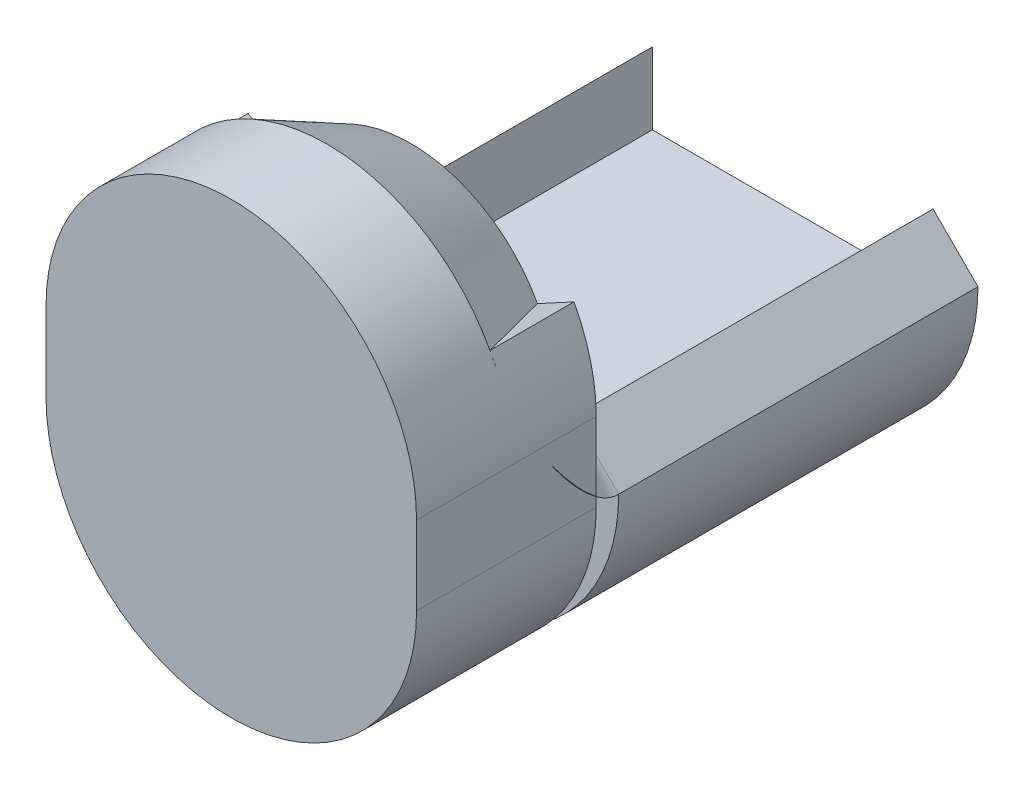
SolidWorks part; units mm, degrees
ref_plane "Front Plane" through (0, 0, 0) normal (0, 0, 1) x (1, 0, 0)
ref_plane "Top Plane" through (0, 0, 0) normal (0, 1, 0) x (1, 0, 0)
ref_plane "Right Plane" through (0, 0, 0) normal (1, 0, 0) x (0, 0, -1)
sketch "Sketch2" plane through (0, 0, 0) normal (0, 0, 1) x (1, 0, 0)
  line L2 (-55.5625, -10.3188) -> (-55.5625, 10.3187)
  line L4 (55.5625, -10.3187) -> (55.5625, 10.3188)
  line L5 (-55.5625, -10.3188) -> (55.5625, 10.3188) construction
  line L6 (-55.5625, 10.3187) -> (55.5625, -10.3187) construction
  arc A0 (-55.5625, 10.3187) -> (55.5625, 10.3188) centre (0, 10.3187) cw
  arc A1 (55.5625, -10.3187) -> (-55.5625, -10.3188) centre (0, -10.3188) cw
  point P0 (0, 0)
  point P7 (0, 65.8812)
  point P8 (0, -65.8813)
  dimension "D1" = 111.125
  dimension "D2" = 131.7625
sketch "Sketch1" plane through (0, 0, 0) normal (0, 0, 1) x (1, 0, 0)
  line L0 (-39.7308, -2.54) -> (39.6442, -2.54)
  line L1 (-39.7308, -2.54) -> (-39.7308, 17.78)
  line L2 (-39.7308, 17.78) -> (-52.4308, 5.08)
  line L3 (39.6442, -2.54) -> (39.6442, 17.78)
  line L4 (39.6442, 17.78) -> (52.3442, 5.08)
  line L5 (-52.4308, 5.08) -> (-52.4308, 78.8001) construction
  line L6 (52.3442, 5.08) -> (52.3442, 85.3232) construction
  circle A0 centre (0, 26.67) radius 28.575
  arc A1 (-52.4308, 5.08) -> (52.3442, 5.08) centre (-0.0433, 5.08) ccw
  circle A2 centre (0, 26.67) radius 33.3375 construction
  dimension "D1" = 57.15
  dimension "D2" = 66.675
  dimension "D3" = 12.7
  dimension "D4" = 45
  dimension "D6" = 20.32
  dimension "D8" = 26.67
  dimension "D5" = 79.375
  dimension "D7" = 29.21
extrude "Boss-Extrude1" add sketch "Sketch1" along normal blind 101.6 contours A1 L4 L3 L0 L1 L2
sketch "Sketch4" plane through (0, 0, 0) normal (0, 0, 1) x (1, 0, 0)
  circle A0 centre (0, 26.67) radius 28.575
  circle A1 centre (0, 26.67) radius 28.575 construction
ref_plane "Plane1" through (0, 0, 158.75) normal (0, 0, 1) x (1, 0, 0)
ref_axis "Axis1" through (0, 26.67, 0) along (0, 0, 1)
sketch "Sketch3" plane through (0, 0, 158.75) normal (0, 0, 1) x (1, 0, 0)
  line L0 (-52.4308, 5.08) -> (-52.4308, 27.305)
  line L1 (52.3442, 5.08) -> (52.3442, 27.305)
  arc A0 (-52.4308, 5.08) -> (52.3442, 5.08) centre (-0.0433, 5.08) ccw
  arc A1 (-52.4308, 5.08) -> (52.3442, 5.08) centre (-0.0433, 5.08) ccw construction
  arc A2 (-52.4308, 27.305) -> (52.3442, 27.305) centre (-0.0433, 27.305) cw
  point P10 (-0.0433, 79.6925)
  point P11 (-0.0433, -47.3075)
  dimension "D1" = 127
extrude "Boss-Extrude2" add sketch "Sketch3" against normal blind 50.8 separate body
sketch "Sketch6" plane through (0, 0, 0) normal (1, 0, 0) x (0, 0, -1)
  line L0 (-131.704, 79.6925) -> (-107.95, 67.945)
  line L1 (-107.95, 79.6925) -> (-158.75, 79.6925) construction
  line L2 (-107.95, 27.305) -> (-107.95, 79.6925) construction
  line L3 (0, 26.67) -> (-68.0102, 26.67) construction
  line L4 (-131.704, 79.6925) -> (-107.95, 79.6925)
  line L5 (-107.95, 79.6925) -> (-107.95, 67.945)
  dimension "D1" = 41.275
sketch "Sketch7" plane through (0, 0, 158.75) normal (0, 0, 1) x (1, 0, 0)
  circle A0 centre (0, 26.67) radius 44.45
  dimension "D1" = 88.9
sketch "Sketch8" plane through (0, 0, 107.95) normal (0, 0, -1) x (-1, 0, 0)
  arc A0 (-46.0519, 52.1984) -> (46.0973, 52.2746) centre (0.0433, 27.305) cw
  arc A1 (52.4308, 27.305) -> (-52.3442, 27.305) centre (0.0433, 27.305) ccw construction
  point P6 (0, 79.6925)
  point P7 (-46.0107, 52.2746)
  point P8 (-40.613, 60.3431)
sweep "Cut-Sweep1" cut profiles "Sketch6" path "Sketch8"
sketch "Sketch9" plane through (0, 0, 0) normal (1, 0, 0) x (0, 0, -1)
  line L2 (-101.6, 5.08) -> (0, 5.08) construction
  line L3 (-131.7039, 79.6925) -> (-131.7039, 52.1984) construction
  spline S0 degree 3 poles (-131.7039, 52.1984) (-131.7039, 40.7492) (-130.8274, 16.7921) (-112.0409, 5.08) (-101.6, 5.08) knots 0 0 0 0 0.578664 1 1 1 1
surface "Surface-Loft3"
equation "\"D1@Sketch2\"=4+3/8"
equation "\"D2@Sketch2\"=5+3/16"
equation "\"D2@Sketch1\"=2+5/8"
equation "\"D1@Boss-Extrude2\"=1+1/8"
